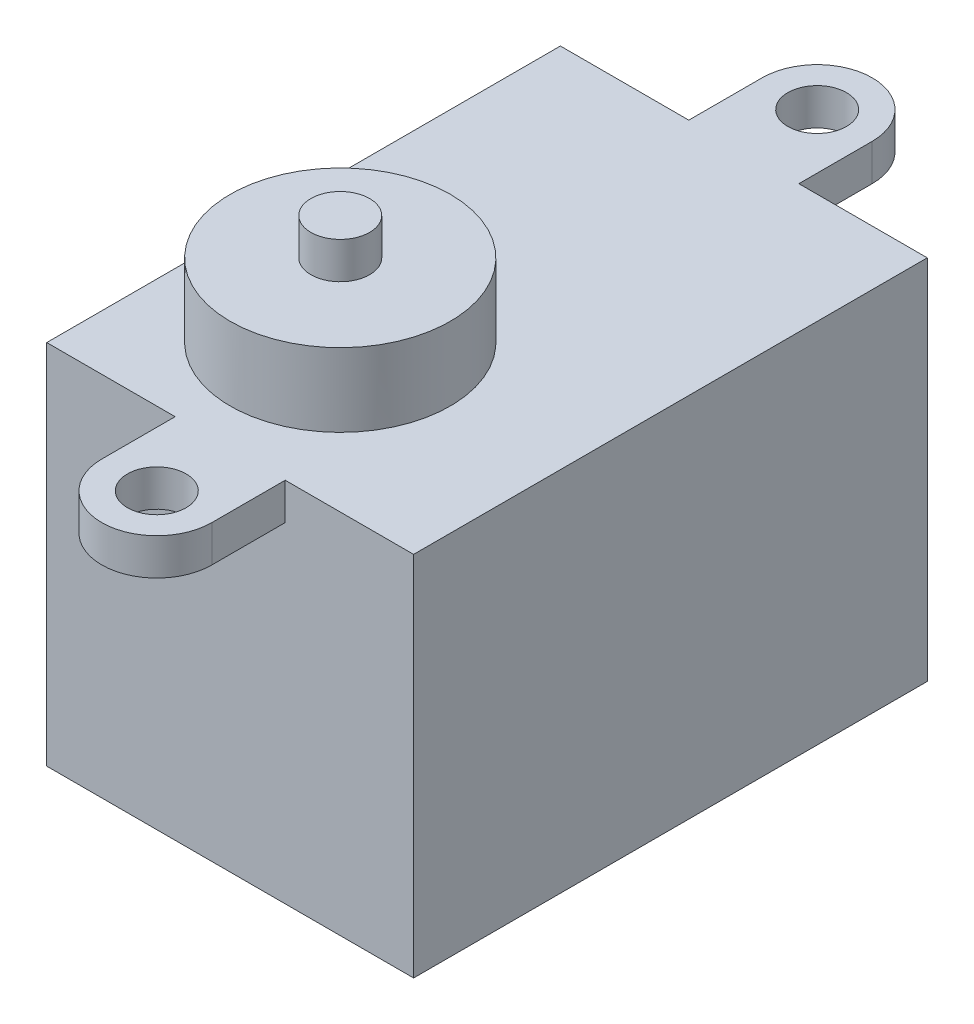
SolidWorks part; units mm, degrees
material "EPDM"
ref_plane "Front Plane" through (0, 0, 0) normal (0, 0, 1) x (1, 0, 0)
ref_plane "Top Plane" through (0, 0, 0) normal (0, 1, 0) x (1, 0, 0)
ref_plane "Right Plane" through (0, 0, 0) normal (1, 0, 0) x (0, 0, -1)
sketch "Sketch1" plane through (0, 0, 0) normal (0, 1, 0) x (1, 0, 0)
  line L1 (0, 0) -> (50, 0)
  line L2 (0, 0) -> (0, 70)
  line L3 (0, 70) -> (50, 70)
  line L4 (50, 0) -> (50, 70)
  dimension "D1" = 50
  dimension "D2" = 70
extrude "Boss-Extrude1" add sketch "Sketch1" along normal blind 50
sketch "Sketch2" plane through (0, 50, 0) normal (0, 1, 0) x (1, 0, 0)
  line L0 (0, 0) -> (50, 0) construction
  line L1 (0, 70) -> (0, 0) construction
  circle A0 centre (20, 20) radius 15
  dimension "D1" = 30
  dimension "D2" = 20
  dimension "D3" = 20
extrude "Boss-Extrude2" add sketch "Sketch2" along normal blind 10
sketch "Sketch3" plane through (0, 60, 0) normal (0, 1, 0) x (1, 0, 0)
  circle A0 centre (20, 20) radius 4
  dimension "D1" = 8
extrude "Boss-Extrude3" add sketch "Sketch3" along normal blind 5
shell "Shell7" thickness 2
sketch "Sketch4" plane through (0, 50, 0) normal (0, 1, 0) x (1, 0, 0)
  line L0 (50, 70) -> (0, 70) construction
  line L1 (17.5, 70) -> (32.5, 70)
  line L2 (17.5, 70) -> (17.5, 80)
  line L4 (32.5, 70) -> (32.5, 80)
  line L5 (25, 0) -> (25, 70) construction
  line L6 (0, 0) -> (50, 0) construction
  arc A0 (32.5, 80) -> (17.5, 80) centre (25, 80) ccw
  circle A1 centre (25, 80) radius 4
  dimension "D3" = 8
  dimension "D1" = 15
  dimension "D2" = 10
extrude "Boss-Extrude4" add sketch "Sketch4" against normal blind 5
ref_plane "Plane1" through (0, 0, -35) normal (0, 0, -1) x (-1, 0, 0)
mirror "Mirror1" about plane through (0, 0, -35) normal (0, 0, -1) of "Boss-Extrude4"
ref_axis "Axis1" through (20, 60, -20) along (0, -1, 0)
scale "Scale1" scale about centroid uniform scaling yes scale factor 0.5
